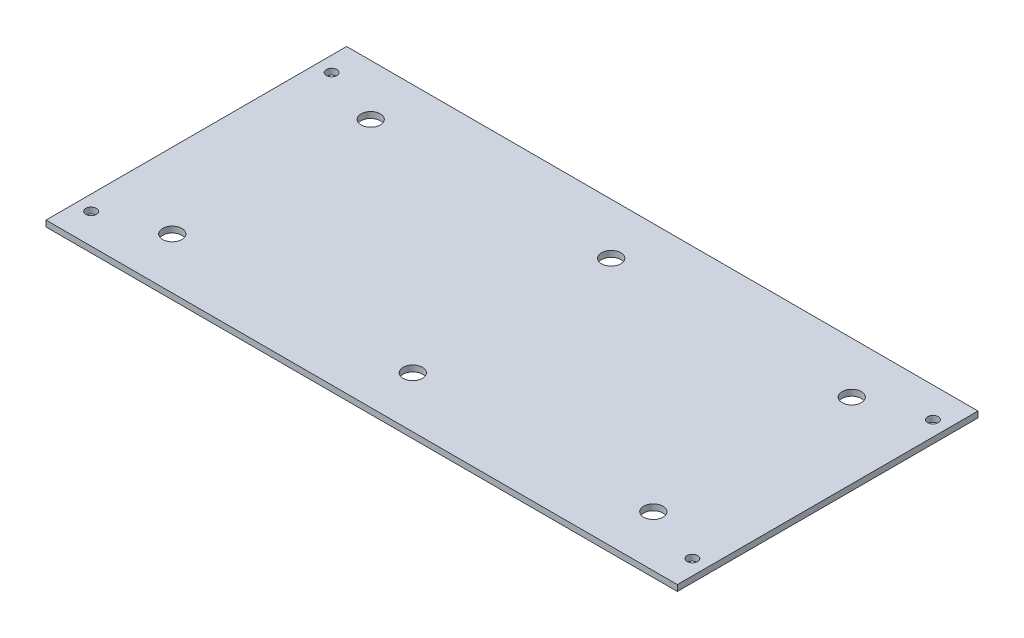
SolidWorks part; units mm, degrees
material "1060 Сплав"
ref_plane "Спереди" through (0, 0, 0) normal (0, 0, 1) x (1, 0, 0)
ref_plane "Сверху" through (0, 0, 0) normal (0, 1, 0) x (1, 0, 0)
ref_plane "Справа" through (0, 0, 0) normal (1, 0, 0) x (0, 0, -1)
sketch "Эскиз1" plane through (0, 0, 0) normal (0, 1, 0) x (1, 0, 0)
  line L5 (0, 0) -> (210, 0)
  line L6 (0, 0) -> (0, 100)
  line L7 (0, 100) -> (210, 100)
  line L8 (210, 0) -> (210, 100)
  line L9 (0, 50) -> (210, 50) construction
  line L10 (105, 100) -> (105, 0) construction
  circle A0 centre (105, 17) radius 3.2
  circle A1 centre (185, 17) radius 3.2
  circle A2 centre (25, 17) radius 3.2
  circle A3 centre (25, 83) radius 3.2
  circle A4 centre (105, 83) radius 3.2
  circle A5 centre (185, 83) radius 3.2
  circle A6 centre (5, 10) radius 1.75
  circle A7 centre (5, 90) radius 1.75
  circle A8 centre (205, 10) radius 1.75
  circle A9 centre (205, 90) radius 1.75
  dimension "D3" = 17
  dimension "D5" = 6.4
  dimension "D6" = 6.4
  dimension "D7" = 3.5
  dimension "D1" = 210
  dimension "D2" = 100
  dimension "D4" = 80
  dimension "D8" = 10
  dimension "D9" = 5
extrude "Бобышка-Вытянуть1" add sketch "Эскиз1" along normal blind 2
